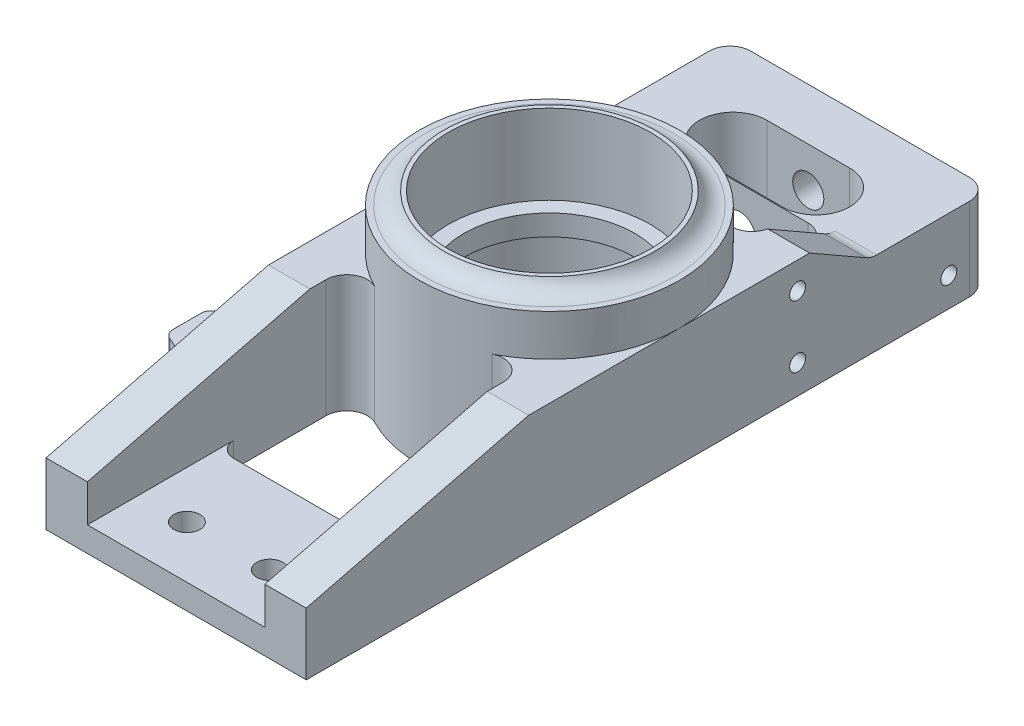
SolidWorks part; units mm, degrees
material "6061-T6 (SS)"
ref_plane "X-Y Datum" through (0, 0, 0) normal (0, 0, 1) x (1, 0, 0)
ref_plane "X-Z Datum" through (0, 0, 0) normal (0, 1, 0) x (1, 0, 0)
ref_plane "Y-Z Datum" through (0, 0, 0) normal (1, 0, 0) x (0, 0, -1)
sketch3d "KPI Sketch"
  line L0 (0, 0, 0) -> (0, 0, 50000) construction
  line L1 (0, 0, 0) -> (0, -50000, 0) construction
  line L2 (0, 0, 0) -> (-50000, 0, 0) construction
  line L3 (0, 17.0188, 98.425) -> (0, -42.747, -247.2184) construction
  line L8 (0, 17.0188, 98.425) -> (0, 17.0188, -69.0361) construction
  line L9 (0, -11.9372, -69.0361) -> (0, 17.0188, -69.0361) construction
  circle A0 centre (0, 0, 0) radius 127 construction
  point P11 (0, -11.9372, -69.0361)
  point P18 (0, 0, 0)
  point P22 (0, 127, 0)
  dimension "D5" = 98.425
  dimension "D8" = 254
  dimension "D2" = 169.9461
  dimension "D3" = 28.956
ref_axis "Wheel Spin Axis" through (0, -55.5512, 0) along (0, 1, 0)
sketch "Bearing Sketch" plane through (0, 0, 0) normal (1, 0, 0) x (0, 0, -1)
  line L11 (0, 0) -> (0, -50000) construction
  line L17 (-30.9994, -25.0922) -> (-39.8894, -25.0922)
  line L23 (-30.9994, -3.175) -> (-26.2369, -3.175)
  line L24 (55.1739, 0) -> (-55.1739, 0) construction
  line L26 (-30.9994, -3.175) -> (-30.9994, -25.0922)
  line L27 (-30.9994, 27.6332) -> (-30.9994, 3.175)
  line L28 (-30.9994, 3.175) -> (-26.2369, 3.175)
  line L29 (-26.2369, 3.175) -> (-26.2369, -3.175)
  line L31 (0, 0) -> (-50000, 0) construction
  line L33 (-30.9994, 27.6332) -> (-32.2694, 27.6332)
  line L34 (-32.2694, 27.6332) -> (-32.2694, 23.7622)
  line L35 (-32.2694, 23.7622) -> (-39.8894, 23.7622)
  line L36 (-39.8894, 23.7622) -> (-39.8894, -25.0922)
  point P3 (-26.2369, 0)
  dimension "D2" = 6.35
  dimension "D1" = 21.9172
  dimension "D4" = 24.4582
  dimension "D3" = 52.4739
  dimension "D6" = 61.9989
  dimension "D5" = 79.7789
  dimension "D7" = 64.5389
  dimension "D8" = 48.8544
revolve "Bearing Dimensions" add sketch "Bearing Sketch" angle 360 about axis through (0, -55.5512, 0) along (0, 1, 0)
sketch "UBJ Material Sketch" plane through (0, -25.0922, 0) normal (0, 1, 0) x (1, 0, 0)
  line L1 (39.8894, -46.2394) -> (-39.8894, -46.2394)
  line L3 (0, 0) -> (-50000, 0) construction
  line L4 (0, 0) -> (0, -50000) construction
  line L5 (39.8894, 0) -> (39.8894, -46.2394)
  line L7 (-39.8894, 0) -> (-39.8894, -46.2394)
  circle A0 centre (0, 0) radius 39.8894 construction
  circle A1 centre (0, 0) radius 39.8894 construction
  arc A2 (-39.8894, 0) -> (39.8894, 0) centre (0, 0) ccw
  point P5 (0, -46.2394)
  point P15 (0, -39.8894)
  dimension "D1" = 6.35
extrude "UBJ Material" add sketch "UBJ Material Sketch" along normal offset from surface (36.1544 mm away) 12.7 up to face at (0, 23.7622, -39.8894)
sketch "Sketch58" plane through (39.8894, 0, 0) normal (1, 0, 0) x (0, 0, -1)
  line L0 (0, 0) -> (-50000, 0) construction
  line L5 (0, 0) -> (0, 50000) construction
  line L14 (-46.2394, 11.0622) -> (-114.4384, -6.0422)
  line L16 (-114.4384, -6.0422) -> (-114.4384, -25.0922)
  line L17 (-114.4384, -25.0922) -> (-62.9981, -25.0922)
  line L18 (-62.9981, -25.0922) -> (-46.2394, -25.0922)
  line L19 (-46.2394, -25.0922) -> (-46.2394, 11.0622)
  line L22 (-46.2394, -25.0922) -> (0, -25.0922) construction
  point P27 (-114.4384, -15.5672)
  dimension "D1" = 19.05
  dimension "D2" = 68.199
extrude "Boss-Extrude6" add sketch "Sketch58" against normal up to surface (79.7789 mm away) contours L16 L17 L18 L19 L14 up to face at (-39.8894, -7.015, 23.1197)
sketch "Sketch9" plane through (0, -25.0922, 0) normal (0, -1, 0) x (1, 0, 0)
  line L3 (-39.8894, 0) -> (-39.8894, 114.4384) construction
  line L4 (-39.8894, 0) -> (-39.8894, 114.4384) construction
  line L5 (0, 0) -> (-50000, 0) construction
  line L7 (-27.1894, 29.1874) -> (-27.1894, 74.3672)
  line L12 (27.1894, 74.3672) -> (-27.1894, 74.3672)
  line L13 (27.1894, 74.3672) -> (27.1894, 29.1874)
  line L17 (39.8894, 114.4384) -> (39.8894, 0) construction
  line L21 (39.8894, 114.4384) -> (39.8894, 0) construction
  arc A2 (39.8894, 0) -> (-39.8894, 0) centre (0, 0) ccw construction
  arc A3 (27.1894, 29.1874) -> (-27.1894, 29.1874) centre (0, 0) ccw
  dimension "D1" = 12.7
  dimension "D2" = 12.7
extrude "UBJ Cross Member" cut sketch "Sketch9" against normal through all contours A3 L13 L12 L7 region at (0, -25.0922, 55.3249)
ref_plane "Plane1" through (0, 4.0077, 0) normal (0, -1, 0) x (-1, 0, 0)
sketch "Sketch10" plane through (0, 4.0077, -1.6553) normal (0, 1, 0) x (1, 0, 0)
  line L7 (-39.8894, -116.0937) -> (39.8894, -116.0937) construction
  line L9 (27.1894, -70.3737) -> (-27.1894, -70.3737)
  line L10 (27.1894, -70.3737) -> (27.1894, -116.0937)
  line L11 (27.1894, -116.0937) -> (-27.1894, -116.0937)
  line L12 (-27.1894, -70.3737) -> (-27.1894, -116.0937)
  line L13 (27.1894, -47.8947) -> (27.1894, -76.0225) construction
  dimension "D1" = 45.72
extrude "UBJ Mass Removal" cut sketch "Sketch10" against normal offset from surface (21.4799 mm away) 7.62 up to face at (0, -25.0922, 47.2469)
fillet "Fillet43" radius 4.7625 2 edges at (-27.1894, -21.2822, 74.3672) (27.1894, -21.2822, 74.3672)
fillet "Fillet26" radius 6.35 2 edges at (-27.1894, -7.015, 29.1874) (27.1894, -7.015, 29.1874)
fillet "Fillet45" [suppressed] radius 5.08
sketch "Sketch4" plane through (0, -25.0922, 0) normal (0, -1, 0) x (1, 0, 0)
  line L1 (-39.8894, -95.25) -> (39.8894, -95.25)
  line L3 (39.8894, 0) -> (39.8894, -95.25)
  line L4 (10.3505, 0) -> (-10.3505, 0) construction
  line L5 (0, 0) -> (0, 50000) construction
  line L7 (-39.8894, 0) -> (-39.8894, -82.55)
  line L9 (-39.8894, -95.25) -> (-39.8894, -82.55)
  arc A0 (-39.8894, 0) -> (39.8894, 0) centre (0, 0) ccw construction
  arc A1 (-39.8894, 0) -> (39.8894, 0) centre (0, 0) ccw
  point P3 (0, 0)
  dimension "D1" = 95.25
  dimension "D4" = 82.55
extrude "LBJ Material" add sketch "Sketch4" against normal offset from surface (36.1544 mm away) 12.7 up to face at (0, 23.7622, -39.8894)
sketch "Sketch7" plane through (0, -25.0922, 0) normal (0, -1, 0) x (1, 0, 0)
  line L1 (-27.1894, -58.42) -> (27.1894, -58.42)
  line L3 (0, 0) -> (50000, 0) construction
  line L4 (27.1894, -29.1874) -> (27.1894, -58.42)
  line L6 (0, 0) -> (0, 50000) construction
  line L8 (39.8894, 0) -> (39.8894, -95.25) construction
  line L9 (-27.1894, -58.42) -> (-27.1894, -29.1874)
  line L11 (-39.8894, -95.25) -> (-39.8894, 0) construction
  arc A4 (-39.8894, 0) -> (39.8894, 0) centre (0, 0) ccw construction
  arc A5 (-39.8894, 0) -> (39.8894, 0) centre (0, 0) ccw
  dimension "D1" = 12.7
  dimension "D2" = 12.7
  dimension "D3" = 58.42
extrude "Cross Members" cut sketch "Sketch7" against normal up to surface (48.8544 mm away) contours L1 region at (0, -25.0922, -47.258) up to face at (0, 23.7622, -39.8894)
sketch "Sketch62" plane through (0, 0, -95.25) normal (0, 0, -1) x (-1, 0, 0)
  line L1 (-27.1894, 0.3078) -> (27.1894, 0.3078)
  line L2 (-27.1894, 0.3078) -> (-27.1894, 11.0622)
  line L3 (-27.1894, 11.0622) -> (27.1894, 11.0622)
  line L4 (27.1894, 0.3078) -> (27.1894, 11.0622)
  line L5 (-39.8894, 11.0622) -> (-39.8894, -25.0922) construction
  dimension "D1" = 12.7
extrude "Cut-Extrude1" cut sketch "Sketch62" against normal blind 44.45
sketch "Sketch5" plane through (0, -25.0922, 0) normal (0, -1, 0) x (1, 0, 0)
  line L0 (0, 0) -> (50000, 0) construction
  line L1 (0, 0) -> (0, 50000) construction
  line L2 (12.7, -69.0361) -> (-12.7, -69.0361) construction
  line L3 (12.7, -79.3612) -> (-12.7, -79.3612)
  line L4 (12.7, -58.711) -> (-12.7, -58.711)
  arc A0 (12.7, -79.3612) -> (12.7, -58.711) centre (12.7, -69.0361) ccw
  arc A1 (-12.7, -58.711) -> (-12.7, -79.3612) centre (-12.7, -69.0361) ccw
  point P8 (0, -69.0361)
  dimension "D2" = 10.3251
  dimension "D1" = 12.7
extrude "LBJ Opening" cut sketch "Sketch5" against normal up to surface (25.4 mm away) up to face at (0, 0.3078, -76.835)
fillet "LBJ Outside" radius 6.35 2 edges at (39.8894, -7.015, -95.25) (-39.8894, -7.015, -95.25)
fillet "LBJ Ramp" radius 6.35 4 edges at (-27.1894, -12.3922, -58.42) (27.1894, -12.3922, -58.42) (-27.1894, -7.015, -29.1874) (27.1894, -7.015, -29.1874)
fillet "BH Lip" radius 6.35 1 edges at (0, 23.7622, -32.2694)
hole_wizard "Ø8.0mm Dowel Hole1" positions "Sketch25" profile "Sketch26" hole size "Ø8.0" standard "ANSI Metric"
sketch "Sketch25" plane through (0, -17.4722, 0) normal (0, 1, 0) x (1, 0, 0)
  line L0 (12.7, -98.425) -> (-12.7, -98.425) construction
  line L2 (0, 200000) -> (0, -250000) construction
  line L5 (0, 0) -> (0, -50000) construction
  line L6 (0, 0) -> (-50000, 0) construction
  point P0 (12.7, -98.425)
  point P2 (-12.7, -98.425)
  dimension "D1" = 12.7
  dimension "D2" = 12.7
  dimension "D3" = 98.425
sketch "Sketch26" plane through (12.7, -17.4722, 98.425) normal (1, 0, 0) x (0, 0, 1)
  line L0 (0, 0) -> (0, 16.002)
  line L1 (0, 16.002) -> (4, 13.5986)
  line L2 (4, 13.5986) -> (4, 0)
  line L5 (4, 0) -> (0, 0)
  line L10 (0, 16.002) -> (-4, 13.5986) construction
  line L11 (0, -6.35) -> (0, 107.95) construction
  dimension "Hole Dia." = 8
  dimension "Hole Depth" = 16.002
  dimension "Drill Angle" = 118
sketch "Sketch30" plane through (0, -25.0922, 0) normal (0, -1, 0) x (1, 0, 0)
  line L1 (0, 0) -> (-50000, 0) construction
  line L2 (0, 0) -> (0, 50000) construction
  line L6 (-39.8894, -31.4891) -> (-39.8894, -65.3856)
  line L18 (-63.4528, -56.9861) -> (-53.5589, -60.5129)
  line L19 (-63.4528, -43.0161) -> (-39.8894, -31.4891)
  line L20 (-63.4197, 41.3533) -> (-39.8894, 30.3086)
  line L21 (-63.4197, 54.04) -> (-39.8894, 64.2936)
  line L22 (-39.8894, 64.2936) -> (-39.8894, 30.3086)
  line L23 (-53.5589, -60.5129) -> (-39.8894, -65.3856)
  line L24 (-63.4528, -43.0161) -> (-63.4528, -56.9861)
  line L25 (-63.4197, 54.04) -> (-63.4197, 41.3533)
  line L27 (-39.8894, -88.9) -> (-39.8894, 0) construction
  line L28 (-39.8894, 46.2394) -> (-39.8894, 0) construction
  line L29 (-39.8894, -88.9) -> (-39.8894, 114.4384) construction
  circle A2 centre (-55.6468, -48.8308) radius 3 construction
  circle A3 centre (-55.6468, 47.1692) radius 3 construction
  point P50 (-55.6468, -48.8308)
  point P51 (-55.6468, 47.1692)
  dimension "D1" = 96
  dimension "D2" = 55.6468
  dimension "D3" = 6
extrude "Boss-Extrude1" add sketch "Sketch30" against normal blind 10.16
fillet "Fillet33" radius 3.175 4 edges at (-63.4197, -20.0122, 41.3533) (-63.4197, -20.0122, 54.04) (-63.4528, -20.0122, -43.0161) (-63.4528, -20.0122, -56.9861)
fillet "Fillet34" radius 6.35 4 edges at (-39.8894, -20.0122, -65.3856) (-39.8894, -20.0122, -31.4891) (-39.8894, -20.0122, 30.3086) (-39.8894, -20.0122, 64.2936)
hole_wizard "CBORE for M8 Hex Head Bolt1" positions "Sketch32" profile "Sketch33" counterbore size "M8" standard "ANSI Metric"
sketch "Sketch32" plane through (0, -25.0922, 0) normal (0, 1, 0) x (1, 0, 0)
  point P9 (-55.6468, -47.1692)
  point P12 (-55.6468, 48.8308)
sketch "Sketch33" plane through (-55.6468, -25.0922, 47.1692) normal (1, 0, 0) x (0, 0, -1)
  line L0 (0, 0) -> (0, 16.002)
  line L1 (0, 16.002) -> (4.2, 13.4784)
  line L2 (4.2, 13.4784) -> (4.2, 5)
  line L3 (4.2, 5) -> (6.75, 5)
  line L4 (6.75, 5) -> (6.75, 0)
  line L5 (6.75, 0) -> (0, 0)
  line L10 (0, 16.002) -> (-4.2, 13.4784) construction
  line L11 (0, -6.35) -> (0, 107.95) construction
  dimension "Hole Dia." = 8.4
  dimension "Hole Depth" = 16.002
  dimension "C'Bore Dia." = 13.5
  dimension "C'Bore Depth" = 5
  dimension "Drill Angle" = 118
chamfer "Chamfer1" [suppressed] distance 1.5875 angle 45
sketch "Sketch34" plane through (0, -25.0922, 0) normal (0, -1, 0) x (1, 0, 0)
  circle A0 centre (0, 0) radius 50.4825 construction
  circle A1 centre (50.4825, 0) radius 5.9531 construction
  point P3 (50.4825, 0)
  dimension "D1" = 100.965
  dimension "D3" = 11.9062
sketch "Sketch37" plane through (0, -25.0922, 0) normal (0, -1, 0) x (1, 0, 0)
  line L1 (-39.8894, -88.9) -> (-39.8894, 0) construction
  line L5 (-39.8894, -11.1125) -> (-58.9394, -11.1125)
  line L10 (-39.8894, -11.1125) -> (-39.8894, 11.1125)
  line L12 (-39.8894, 11.1125) -> (-58.9394, 11.1125)
  line L13 (-58.9394, -11.1125) -> (-58.9394, 11.1125)
  line L15 (200000, 0) -> (-250000, 0) construction
  point P7 (-58.9394, 0)
  dimension "D2" = 19.05
  dimension "D3" = 22.225
extrude "Speed Sensor Extrude" add sketch "Sketch37" against normal blind 7.716
hole_wizard "3/8 (0.375) Diameter Hole2" positions "Sketch50" profile "Sketch51" hole size "3/8" standard "ANSI Inch"
sketch "Sketch50" plane through (0, 0, -95.25) normal (0, 0, -1) x (-1, 0, 0)
  point P0 (0, -11.9372)
sketch "Sketch51" plane through (0, -11.9372, -95.25) normal (1, 0, 0) x (0, 1, 0)
  line L0 (0, 0) -> (0, 39.6916)
  line L1 (0, 39.6916) -> (4.7625, 36.83)
  line L2 (4.7625, 36.83) -> (4.7625, 0)
  line L5 (4.7625, 0) -> (0, 0)
  line L10 (0, 39.6916) -> (-4.7625, 36.83) construction
  line L11 (0, -6.35) -> (0, 107.95) construction
  dimension "Hole Dia." = 9.525
  dimension "Hole Depth" = 36.83
  dimension "Drill Angle" = 118
fillet "Fillet47" radius 6.35 4 edges at (-39.8894, -21.2341, 11.1125) (-58.9394, -21.2341, 11.1125) (-39.8894, -21.2341, -11.1125) (-58.9394, -21.2341, -11.1125)
hole_wizard "15/32 (0.46875) Diameter Hole1" positions "Sketch35" profile "Sketch36" hole size "15/32" standard "ANSI Inch"
sketch "Sketch35" plane through (0, -17.3761, 0) normal (0, 1, 0) x (1, 0, 0)
  line L0 (200000, 0) -> (-250000, 0) construction
  circle A0 centre (0, 0) radius 50.4825 construction
  point P0 (-50.4825, 0)
sketch "Sketch36" plane through (-50.4825, -17.3761, 0) normal (1, 0, 0) x (0, 0, 1)
  line L0 (0, 0) -> (0, 16.002)
  line L1 (0, 16.002) -> (5.9531, 12.425)
  line L2 (5.9531, 12.425) -> (5.9531, 0)
  line L5 (5.9531, 0) -> (0, 0)
  line L10 (0, 16.002) -> (-5.9531, 12.425) construction
  line L11 (0, -6.35) -> (0, 107.95) construction
  dimension "Hole Dia." = 11.9062
  dimension "Hole Depth" = 16.002
  dimension "Drill Angle" = 118
fillet "Fillet49" [suppressed] radius 4.7625
sketch "Sketch59" plane through (39.8894, 0, 0) normal (-1, 0, 0) x (0, 0, 1)
  line L0 (114.4384, -25.0922) -> (-88.9, -25.0922) construction
  line L1 (-95.25, 11.0622) -> (-95.25, -25.0922) construction
  point P0 (-36.195, 2.8478)
  point P1 (-36.195, -16.2022)
  point P4 (-82.55, -16.2022)
  dimension "D1" = 19.05
  dimension "D2" = 46.355
  dimension "D3" = 8.89
  dimension "D4" = 12.7
hole_wizard "#10 (0.1935) Diameter Hole1" positions "Sketch60" profile "Sketch61" hole size "#10" standard "ANSI Inch"
sketch "Sketch60" plane through (39.8894, 0, 0) normal (-1, 0, 0) x (0, 0, 1)
  point P0 (-82.55, -16.2022)
  point P6 (-36.195, 2.8478)
  point P9 (-36.195, -16.2022)
sketch "Sketch61" plane through (39.8894, -16.2022, -82.55) normal (0, 1, 0) x (0, 0, -1)
  line L0 (0, 0) -> (0, 11.1125)
  line L1 (0, 11.1125) -> (2.4574, 9.6359)
  line L2 (2.4574, 9.6359) -> (2.4574, 0)
  line L5 (2.4574, 0) -> (0, 0)
  line L10 (0, 11.1125) -> (-2.4575, 9.6359) construction
  line L11 (0, -6.35) -> (0, 107.95) construction
  dimension "Hole Dia." = 4.9149
  dimension "Hole Depth" = 11.1125
  dimension "Drill Angle" = 118
sketch "Sketch63" plane through (-39.8894, 0, 0) normal (-1, 0, 0) x (0, 0, 1)
  line L1 (-88.9, 11.0622) -> (0, 11.0622) construction
  line L2 (-39.8894, 23.7622) -> (-39.8894, -25.0922) construction
  line L5 (-95.25, 0.3078) -> (-58.711, 0.3078)
  line L6 (-58.711, 0.3078) -> (-39.8894, 11.0622)
  line L7 (-39.8894, 11.0622) -> (-95.25, 11.0622)
  line L8 (-95.25, 11.0622) -> (-95.25, 0.3078)
extrude "Cut-Extrude2" cut sketch "Sketch63" against normal through all
fillet "Fillet50" radius 6.35 2 edges at (33.5394, 0.3078, -58.711) (-33.5394, 0.3078, -58.711)
sketch3d "Toe Sketch"
  line L0 (0, -11.9372, -79.3612) -> (0, -11.9372, -95.25) construction
  line L1 (0, -11.9372, -79.3612) -> (66.5226, -11.9372, -79.3612) construction
  line L2 (66.5226, -11.9372, -79.3612) -> (66.5226, -11.9372, -18.9854) construction
  line L3 (66.5226, -11.9372, -18.9854) -> (66.5226, 12.3452, -18.9854) construction
  point P0 (0, -11.9372, -79.3612)
  point P7 (66.5226, 12.3452, -18.9854)
  dimension "D1" = 66.5226
  dimension "D2" = 60.3758
  dimension "D3" = 24.2824
equation "\"KPI\"= 9.56"
equation "\"TOE alng x\"= 77.1mm"
equation "\"x dtm to toe\"= 36.4mm"
equation "\"XY to toe\"= 30.7mm"
equation "\"XZ to LBJ\"= 22.08mm"
equation "\"XY to LBJ\"= 3.2"
equation "\"XY to UBJ\"=3.875"
equation "\"Bearing Inner Bore\"= 1.25'RADIUS"
equation "\"Bearing Outer Bore\"= 2.4409'RADIUS"
equation "\"Bearing Thickness\"= .7150"
equation "\"D1@Bearing Sketch\"=\"Bearing Thickness\" +.25-0.09712-0.005"
equation "\"D4@Bearing Sketch\"=\"Bearing Thickness\" +.2625-0.06458+.05"
equation "\"D3@Bearing Sketch\"=\"Bearing Outer Bore\" - .375"
equation "\"D6@Bearing Sketch\" = \"Bearing Outer Bore\""
equation "\"D5@Bearing Sketch\" = \"Bearing Outer Bore\" + 2 * .35"
equation "\"D7@Bearing Sketch\" = \"Bearing Outer Bore\" + .1"
equation "\"D8@Bearing Sketch\"=\"Bearing Thickness\" * 2 + 0.225 + 0.2684"
equation "\"D1@Sketch4\"=\"XY to LBJ\" + .25+.3"
equation "\"D1Sketch21\"= \"XY to UBJ\" + 0.375"
equation "\"D3@Sketch25\"=\"XY to UBJ\""
equation "\"D5@KPI Sketch\"=\"XY to UBJ\""
